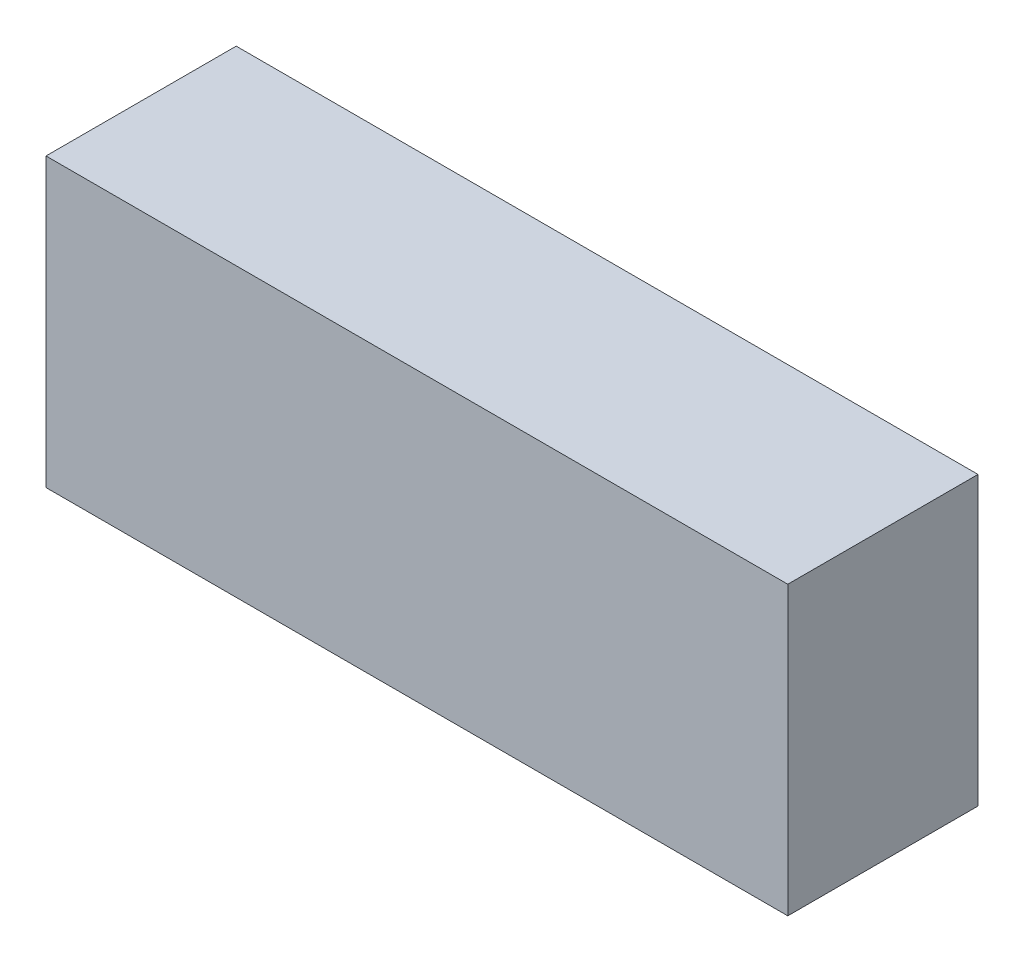
SolidWorks part; units mm, degrees
ref_plane "Front Plane" through (0, 0, 0) normal (0, 0, 1) x (1, 0, 0)
ref_plane "Top Plane" through (0, 0, 0) normal (0, 1, 0) x (1, 0, 0)
ref_plane "Right Plane" through (0, 0, 0) normal (1, 0, 0) x (0, 0, -1)
sketch "Sketch2" plane through (0, 0, 0) normal (0, 0, 1) x (1, 0, 0)
  line L4 (7.6721, -0.2083) -> (7.6721, -56.6083)
  line L5 (7.6721, -56.6083) -> (159.6721, -56.6083)
  line L6 (159.6721, -56.6083) -> (159.6721, -0.2083)
  line L7 (159.6721, -0.2083) -> (7.6721, -0.2083)
  line L8 (7.6721, -0.2083) -> (7.6721, -56.6083)
  line L9 (7.6721, -56.6083) -> (159.6721, -56.6083)
  line L10 (159.6721, -56.6083) -> (159.6721, -0.2083)
  line L11 (159.6721, -0.2083) -> (7.6721, -0.2083)
  dimension "D1" = 0
extrude "Boss-Extrude1" add sketch "Sketch2" along normal blind 2
sketch "Sketch3" plane through (0, 0, 2) normal (0, 0, 1) x (1, 0, 0)
  line L8 (161.6721, 1.7917) -> (5.6721, 1.7917)
  line L9 (5.6721, 1.7917) -> (5.6721, -58.6083)
  line L10 (5.6721, -58.6083) -> (161.6721, -58.6083)
  line L11 (161.6721, -58.6083) -> (161.6721, 1.7917)
  line L12 (161.6721, 1.7917) -> (5.6721, 1.7917)
  line L13 (5.6721, 1.7917) -> (5.6721, -58.6083)
  line L14 (5.6721, -58.6083) -> (161.6721, -58.6083)
  line L15 (161.6721, -58.6083) -> (161.6721, 1.7917)
  line L16 (159.6721, -0.2083) -> (7.6721, -0.2083)
  line L17 (7.6721, -0.2083) -> (7.6721, -56.6083)
  line L18 (7.6721, -56.6083) -> (159.6721, -56.6083)
  line L19 (159.6721, -56.6083) -> (159.6721, -0.2083)
  line L20 (159.6721, -0.2083) -> (7.6721, -0.2083)
  line L21 (7.6721, -0.2083) -> (7.6721, -56.6083)
  line L22 (7.6721, -56.6083) -> (159.6721, -56.6083)
  line L23 (159.6721, -56.6083) -> (159.6721, -0.2083)
  dimension "D1" = 2
  dimension "D2" = 0
extrude "Boss-Extrude2" add sketch "Sketch3" along direction (0, 0, -1) on the side against the normal blind 40
sketch "Sketch4" plane through (0, 0, 0) normal (0, 0, -1) x (-1, 0, 0)
  circle A0 centre (-48.4021, -52.2683) radius 1.6 construction
  circle A1 centre (-48.4021, -52.2683) radius 1.6
  circle A2 centre (-78.8821, -47.1883) radius 1.6 construction
  circle A3 centre (-78.8821, -47.1883) radius 1.6
  circle A4 centre (-78.8821, -19.2483) radius 1.6 construction
  circle A5 centre (-78.8821, -19.2483) radius 1.6
  circle A6 centre (-54.7521, -4.0083) radius 1.6 construction
  circle A7 centre (-54.7521, -4.0083) radius 1.6
  circle A8 centre (-129.6821, -4.0083) radius 1.6 construction
  circle A9 centre (-129.6821, -4.0083) radius 1.6
  circle A10 centre (-130.9521, -52.2683) radius 1.6 construction
  circle A11 centre (-130.9521, -52.2683) radius 1.6
extrude "Boss-Extrude3" add sketch "Sketch4" along normal blind 6
sketch "Sketch5" plane through (0, 0, 0) normal (0, 0, -1) x (-1, 0, 0)
  circle A1 centre (-54.7521, -4.0083) radius 1.6 construction
  circle A2 centre (-48.4021, -52.2683) radius 1.6 construction
  circle A3 centre (-78.8821, -47.1883) radius 1.6 construction
  circle A4 centre (-78.8821, -19.2483) radius 1.6 construction
  circle A5 centre (-129.6821, -4.0083) radius 1.6 construction
  circle A6 centre (-130.9521, -52.2683) radius 1.6 construction
  circle A7 centre (-54.7521, -4.0083) radius 1.6 construction
  circle A8 centre (-48.4021, -52.2683) radius 1.6 construction
  circle A9 centre (-78.8821, -47.1883) radius 1.6 construction
  circle A10 centre (-78.8821, -19.2483) radius 1.6 construction
  circle A11 centre (-129.6821, -4.0083) radius 1.6 construction
  circle A12 centre (-130.9521, -52.2683) radius 1.6 construction
  circle A13 centre (-54.7521, -4.0083) radius 3.6
  circle A14 centre (-48.4021, -52.2683) radius 3.6
  circle A15 centre (-78.8821, -47.1883) radius 3.6
  circle A16 centre (-78.8821, -19.2483) radius 3.6
  circle A17 centre (-129.6821, -4.0083) radius 3.6
  circle A18 centre (-130.9521, -52.2683) radius 3.6
  dimension "D1" = 2
extrude "Boss-Extrude4" add sketch "Sketch5" along normal blind 3
ref_plane "Plane1" through (0, 0, -17.3) normal (0, 0, -1) x (-1, 0, 0)
sketch "Sketch6" plane through (0, 0, 0) normal (0, 0, -1) x (-1, 0, 0)
  line L0 (-7.6721, -28.4083) -> (-159.6721, -28.4083) construction
  line L1 (-7.6721, -0.2083) -> (-7.6721, -56.6083) construction
  line L2 (-159.6721, -56.6083) -> (-159.6721, -0.2083) construction
  line L3 (-7.6721, -56.6083) -> (-22.6721, -56.6083)
  line L4 (-7.6721, -56.6083) -> (-159.6721, -56.6083) construction
  line L5 (-22.6721, -56.6083) -> (-7.6721, -41.6083)
  line L6 (-7.6721, -41.6083) -> (-7.6721, -56.6083)
  line L7 (-7.6721, -15.2083) -> (-7.6721, -0.2083)
  line L8 (-22.6721, -0.2083) -> (-7.6721, -15.2083)
  line L9 (-7.6721, -0.2083) -> (-22.6721, -0.2083)
  line L10 (-159.6721, -56.6083) -> (-144.6721, -56.6083)
  line L11 (-144.6721, -56.6083) -> (-159.6721, -41.6083)
  line L12 (-159.6721, -41.6083) -> (-159.6721, -56.6083)
  line L13 (-156.9721, -21.9083) -> (-159.6721, -21.9083)
  line L14 (-159.6721, -21.9083) -> (-159.6721, -6.9083)
  line L15 (-159.6721, -6.9083) -> (-156.9721, -6.9083)
  circle A0 centre (-156.9721, -14.4083) radius 0.5 construction
  circle A1 centre (-156.9721, -14.4083) radius 0.5
  arc A2 (-156.9721, -21.9083) -> (-156.9721, -6.9083) centre (-156.9721, -14.4083) ccw
  dimension "D2" = 15
  dimension "D1" = 15
extrude "Boss-Extrude5" add sketch "Sketch6" along normal offset from surface (15.5 mm away) 1.8 up to plane "Plane1"
sketch "Sketch7" plane through (0, 0, 0) normal (0, 0, -1) x (-1, 0, 0)
  circle A0 centre (-9.4721, -2.0083) radius 0.5 construction
  circle A1 centre (-9.4721, -2.0083) radius 0.5 construction
  circle A2 centre (-10.0721, -54.2083) radius 0.5 construction
  circle A3 centre (-10.0721, -54.2083) radius 0.5 construction
  circle A4 centre (-157.5721, -54.5083) radius 0.5 construction
  circle A5 centre (-156.9721, -14.4083) radius 0.5 construction
  circle A6 centre (-157.5721, -54.5083) radius 0.5 construction
  circle A7 centre (-156.9721, -14.4083) radius 0.5 construction
  circle A8 centre (-9.4721, -2.0083) radius 0.4
  circle A9 centre (-10.0721, -54.2083) radius 0.4
  circle A10 centre (-157.5721, -54.5083) radius 0.4
  circle A11 centre (-156.9721, -14.4083) radius 0.4
  dimension "D1" = 0.1
extrude "Boss-Extrude6" add sketch "Sketch7" along normal offset from surface (19.3 mm away) 2 up to plane "Plane1" offset beyond the face yes
